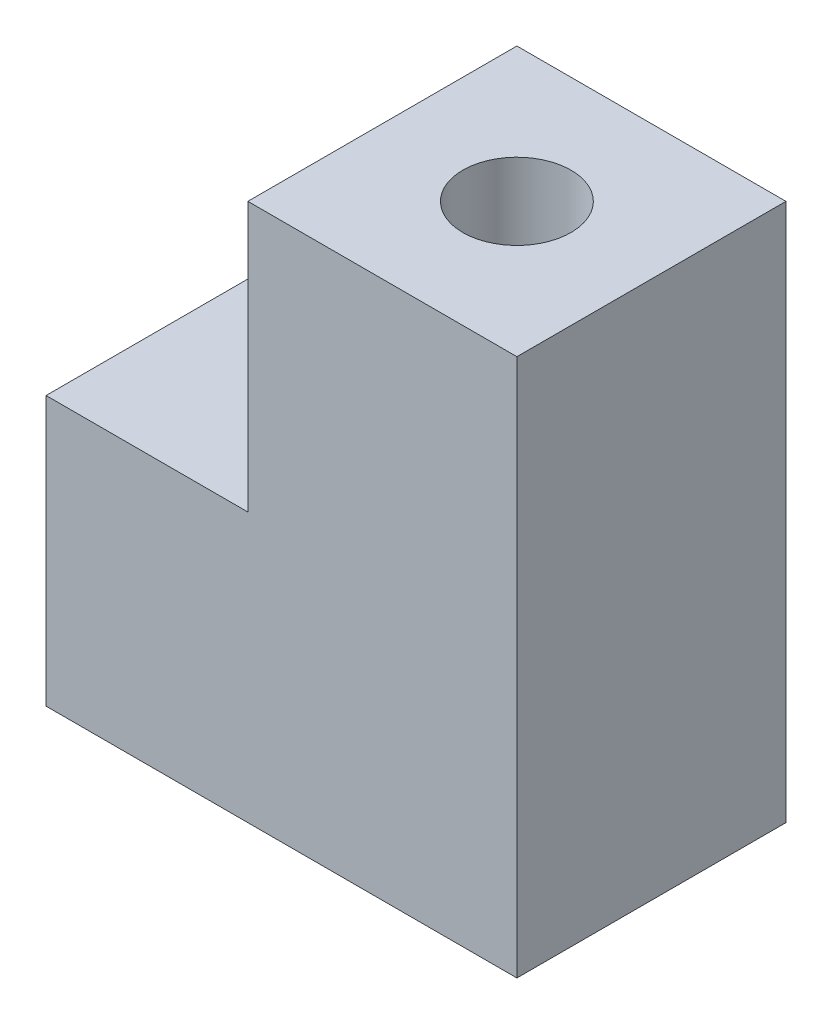
SolidWorks part; units mm, degrees
material "6061-T6 (SS)"
ref_plane "Front" through (0, 0, 0) normal (0, 0, 1) x (1, 0, 0)
ref_plane "Top" through (0, 0, 0) normal (0, 1, 0) x (1, 0, 0)
ref_plane "Right" through (0, 0, 0) normal (1, 0, 0) x (0, 0, -1)
sketch "Sketch1" plane through (0, 0, 0) normal (0, 0, 1) x (1, 0, 0)
  line L0 (0, 0) -> (0, 25.4)
  line L1 (0, 25.4) -> (-12.7, 25.4)
  line L2 (-12.7, 25.4) -> (-12.7, 12.7)
  line L3 (-12.7, 12.7) -> (-22.225, 12.7)
  line L4 (-22.225, 12.7) -> (-22.225, 0)
  line L5 (-22.225, 0) -> (0, 0)
  dimension "D1" = 12.7
  dimension "D2" = 12.7
  dimension "D3" = 25.4
  dimension "D4" = 22.225
extrude "Boss-Extrude1" add sketch "Sketch1" along normal blind 12.7
hole_wizard "1/4-20 Tapped Hole1" positions "Sketch2" profile "Sketch3" tap size "1/4-20" standard "ANSI Inch" end condition through all
sketch "Sketch2" plane through (0, 25.4, 0) normal (0, 1, 0) x (1, 0, 0)
  line L0 (-12.7, 0) -> (0, -12.7) construction
  point P0 (-6.35, -6.35)
sketch "Sketch3" plane through (-6.35, 25.4, 6.35) normal (1, 0, 0) x (0, 0, 1)
  line L0 (0, 0) -> (0, 25.4)
  line L1 (0, 25.4) -> (2.5527, 25.4)
  line L2 (2.5527, 25.4) -> (2.5527, 0)
  line L5 (2.5527, 0) -> (0, 0)
  line L11 (0, -6.35) -> (0, 107.95) construction
  dimension "Thru Tap Drill Dia." = 5.1054
  dimension "Thru Tap Drill Depth" = 25.4
cosmetic thread "Hole Thread1" parameters "D2"=6.35
hole_wizard "1/4-20 Tapped Hole2" positions "Sketch4" profile "Sketch5" tap size "1/4-20" standard "ANSI Inch"
sketch "Sketch4" plane through (-22.225, 0, 0) normal (-1, 0, 0) x (0, 0, 1)
  line L0 (0, 12.7) -> (12.7, 0) construction
  point P0 (6.35, 6.35)
sketch "Sketch5" plane through (-22.225, 6.35, 6.35) normal (0, 1, 0) x (0, 0, 1)
  line L0 (0, 0) -> (0, 18.0438)
  line L1 (0, 18.0438) -> (2.5527, 16.51)
  line L2 (2.5527, 16.51) -> (2.5527, 0)
  line L5 (2.5527, 0) -> (0, 0)
  line L10 (0, 18.0438) -> (-2.5527, 16.51) construction
  line L11 (0, -6.35) -> (0, 107.95) construction
  dimension "Tap Drill Dia." = 5.1054
  dimension "Tap Drill Depth" = 16.51
  dimension "Drill Angle" = 118
cosmetic thread "Hole Thread2" parameters "D1"=12.7, "D2"=6.35
